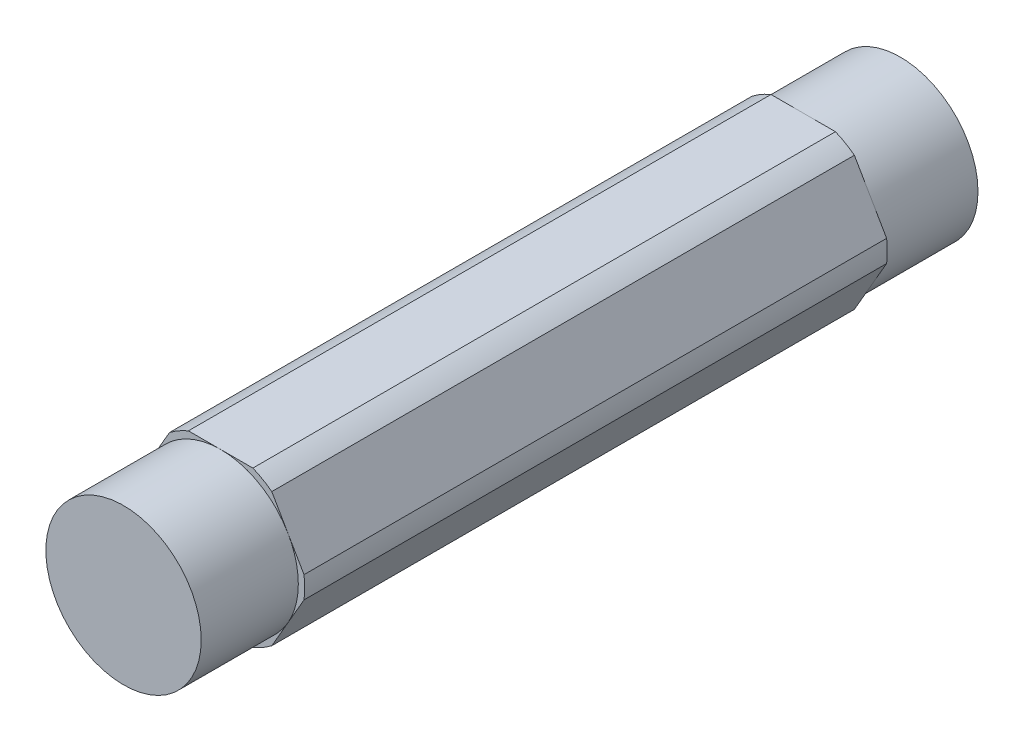
SolidWorks part; units mm, degrees
ref_plane "Front Plane" through (0, 0, 0) normal (0, 0, 1) x (1, 0, 0)
ref_plane "Top Plane" through (0, 0, 0) normal (0, 1, 0) x (1, 0, 0)
ref_plane "Right Plane" through (0, 0, 0) normal (1, 0, 0) x (0, 0, -1)
sketch "Sketch1" plane through (0, 0, 0) normal (0, 0, 1) x (1, 0, 0)
  line L1 (-3.6662, 6.35) -> (-7.3323, 0)
  line L2 (-7.3323, 0) -> (-3.6662, -6.35)
  line L3 (-3.6662, -6.35) -> (3.6662, -6.35)
  line L4 (3.6662, -6.35) -> (7.3323, 0)
  line L5 (7.3323, 0) -> (3.6662, 6.35)
  line L6 (3.6662, 6.35) -> (-3.6662, 6.35)
  circle A0 centre (0, 0) radius 6.875
  circle A1 centre (0, 0) radius 6.35 construction
  point P3 (-7.3231, 0.3672)
  point P11 (0, 0)
  point P12 (0, 6.35)
  dimension "D1" = 12.7
  dimension "D2" = 13.75
extrude "Boss-Extrude1" add sketch "Sketch1" along normal mid plane 63.5 contours L5 A0 L6 L1 L2 L3 L4 region at (0, 0, 0)
sketch "Sketch2" plane through (0, 0, 31.75) normal (0, 0, 1) x (1, 0, 0)
  circle A0 centre (0, 0) radius 6.35
  line M2 (6.8168, 0.893) -> (4.1818, 5.457)
  arc M3 (4.1818, 5.457) -> (2.635, 6.35) centre (0, 0) ccw
  line M4 (2.635, 6.35) -> (-2.635, 6.35)
  arc M5 (-2.635, 6.35) -> (-4.1818, 5.457) centre (0, 0) ccw
  line M6 (-4.1818, 5.457) -> (-6.8168, 0.893)
  arc M7 (-6.8168, 0.893) -> (-6.8168, -0.893) centre (0, 0) ccw
  line M8 (-6.8168, -0.893) -> (-4.1818, -5.457)
  arc M9 (-4.1818, -5.457) -> (-2.635, -6.35) centre (0, 0) ccw
  line M10 (-2.635, -6.35) -> (2.635, -6.35)
  arc M11 (2.635, -6.35) -> (4.1818, -5.457) centre (0, 0) ccw
  line M12 (4.1818, -5.457) -> (6.8168, -0.893)
  arc M13 (6.8168, -0.893) -> (6.8168, 0.893) centre (0, 0) ccw
  dimension "D1" = 12.7
extrude "Cut-Extrude2" cut sketch "Sketch2" against normal blind 7.9375 contours A0 M4 M5 M6 | A0 M2 M3 M4 | A0 M12 M13 M2 | A0 M10 M11 M12 | A0 M8 M9 M10 | A0 M6 M7 M8 region at (6.4637, 0, 31.75) region at (3.2318, 5.5977, 31.75) region at (3.2318, -5.5977, 31.75) region at (-3.2318, 5.5977, 31.75) region at (-3.2318, -5.5977, 31.75) region at (-6.4637, 0, 31.75)
mirror "Mirror1" about plane through (0, 0, 0) normal (0, 0, 1) of "Cut-Extrude2"
equation "\"D2@Sketch1\"=13.75mm"
